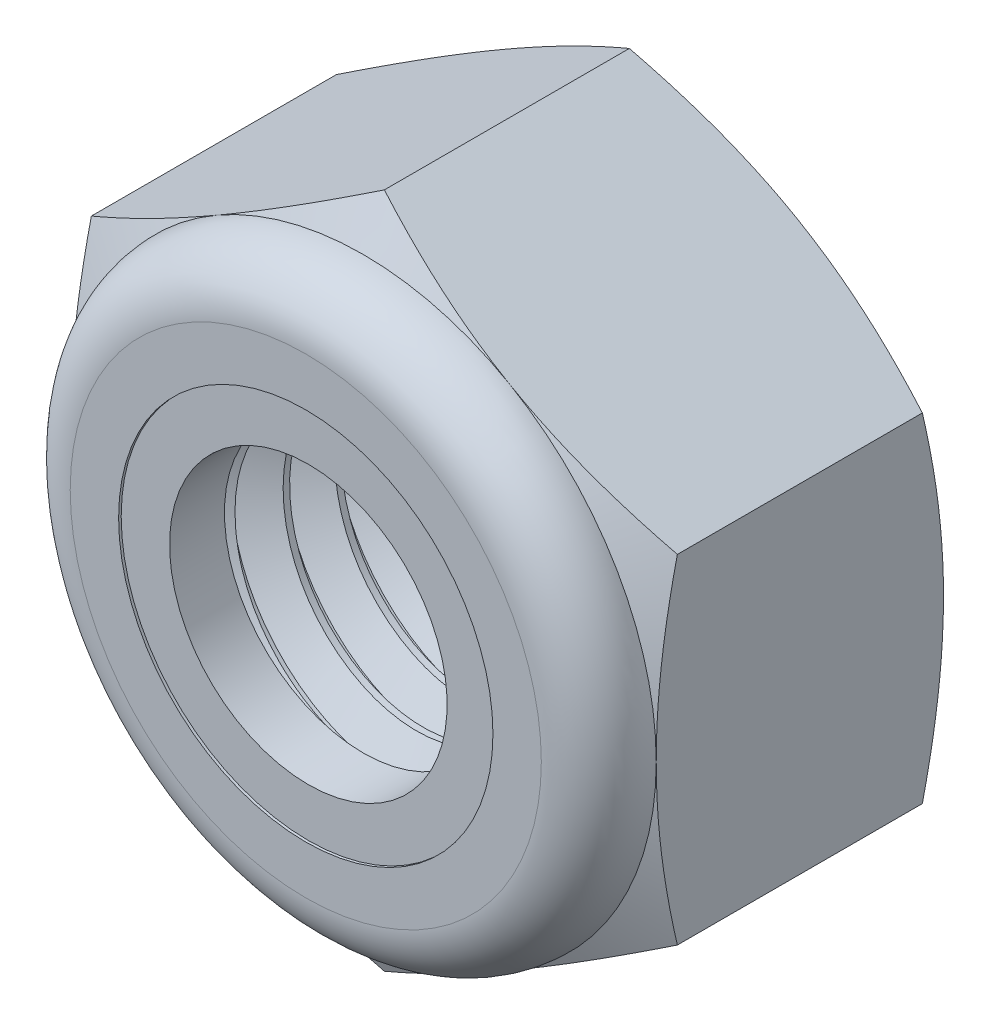
SolidWorks part; units mm, degrees
ref_plane "Front Plane" through (0, 0, 0) normal (0, 0, 1) x (1, 0, 0)
ref_plane "Top Plane" through (0, 0, 0) normal (0, 1, 0) x (1, 0, 0)
ref_plane "Right Plane" through (0, 0, 0) normal (1, 0, 0) x (0, 0, -1)
sketch "Sketch1" plane through (0, 0, 0) normal (0, 0, 1) x (1, 0, 0)
  line L1 (0, 9.815) -> (-8.5, 4.9075)
  line L2 (-8.5, 4.9075) -> (-8.5, -4.9075)
  line L3 (-8.5, -4.9075) -> (0, -9.815)
  line L4 (0, -9.815) -> (8.5, -4.9075)
  line L5 (8.5, -4.9075) -> (8.5, 4.9075)
  line L6 (8.5, 4.9075) -> (0, 9.815)
  circle A0 centre (0, 0) radius 8.5 construction
  circle A1 centre (0, 0) radius 5
  point P10 (0, -5)
  point P11 (0, 5)
  point P12 (0, 8.5)
  dimension "Thread Size" = 10
  dimension "Width" = 17
sketch "Sketch2" plane through (0, 0, 0) normal (1, 0, 0) x (0, 0, -1)
  line L0 (5, 0) -> (-5, 0) construction
  line L1 (-5, 5) -> (5, 5) construction
  line L2 (-4.925, -5.4295) -> (-6.27, -5.4295) construction
  line L3 (-6.4063, 5.1624) -> (-4.9063, 5.1624) construction
  line L4 (-4.9063, 5.1624) -> (-5.6563, 3.8633) construction
  line L5 (-5.6563, 3.8633) -> (-6.4063, 5.1624) construction
  line L6 (-6.3125, 5) -> (-5, 5) construction
  line L7 (-5.75, 4.0257) -> (-5.5625, 4.0257) construction
  line L8 (-5.6563, 4.0257) -> (-5.6563, 3.8633) construction
  line L9 (-5.6563, 5) -> (-5.6563, 5.1624) construction
  line L10 (-4.9531, 5.0812) -> (-6.3594, 5.0812)
  line L11 (-6.3594, 5.0812) -> (-5.75, 4.0257)
  line L12 (-5.75, 4.0257) -> (-5.5625, 4.0257)
  line L13 (-5.5625, 4.0257) -> (-4.9531, 5.0812)
  line L14 (5, 0) -> (6.27, 0)
  line L15 (6.27, 0) -> (6.27, 11.085)
  line L16 (0, 11.085) -> (0, 9.815) construction
  line L17 (0, 9.815) -> (0, 4.9075) construction
  line L18 (5, 8.5) -> (-3.3333, 8.5) construction
  line L19 (-5.75, -4.0257) -> (-5.5625, -4.0257) construction
  line L20 (5, 8.5) -> (5, 0)
  line L21 (4.3868, 9.815) -> (-2.7202, 9.815)
  line L22 (5, 8.5) -> (4.3868, 9.815)
  line L23 (-5, 0) -> (-5, 6.8333) construction
  line L24 (-3.3333, 8.5) -> (-2.7202, 9.815)
  line L25 (6.27, 11.085) -> (-6.27, 11.085)
  line L26 (-5, 6.8333) -> (-6.27, 6.8333)
  line L27 (-6.27, 6.8333) -> (-6.27, 11.085)
  line L28 (-4.925, 6.8333) -> (-4.925, 4.0257) construction
  line L29 (-4.925, 5.4295) -> (-6.27, 5.4295)
  line L30 (-6.27, 5.4295) -> (-6.27, 0)
  line L31 (-6.27, 0) -> (-3.3333, 0)
  line L32 (-3.3333, 0) -> (-3.3333, 8.425)
  line L33 (-4.925, 5.4295) -> (-4.925, 6.8333)
  arc A0 (-3.3333, 8.5) -> (-5, 6.8333) centre (-3.3333, 6.8333) ccw
  arc A1 (-3.3333, 8.425) -> (-4.925, 6.8333) centre (-3.3333, 6.8333) ccw
  point P4 (0, 0)
  point P18 (-5.6563, 5.0812)
  point P22 (-5.6563, 5.0812)
  point P33 (0, 9.815)
  point P48 (-6.27, -5.4295)
  point P51 (-5.75, -4.0257)
  dimension "Height" = 10
  dimension "Pitch" = 1.5
  dimension "D1" = 0.1875
  dimension "D2" = 1.27
  dimension "D3" = 25
  dimension "D4" = 1.6667
  dimension "D5" = 25
  dimension "D6" = 0.075
sketch "Sketch3" plane through (0, 0, 0) normal (0, 0, 1) x (1, 0, 0)
  line L0 (0, -9.815) -> (8.5, -4.9075) construction
  line L1 (8.5, -4.9075) -> (8.5, 4.9075) construction
  line L2 (8.5, 4.9075) -> (0, 9.815) construction
  line L3 (0, 9.815) -> (-8.5, 4.9075) construction
  line L4 (-8.5, 4.9075) -> (-8.5, -4.9075) construction
  line L5 (-8.5, -4.9075) -> (0, -9.815) construction
  line L6 (0, -9.815) -> (8.5, -4.9075)
  line L7 (8.5, -4.9075) -> (8.5, 4.9075)
  line L8 (8.5, 4.9075) -> (0, 9.815)
  line L9 (0, 9.815) -> (-8.5, 4.9075)
  line L10 (-8.5, 4.9075) -> (-8.5, -4.9075)
  line L11 (-8.5, -4.9075) -> (0, -9.815)
  circle A0 centre (0, 0) radius 5 construction
  circle A1 centre (0, 0) radius 5
extrude "Boss-Extrude1" add sketch "Sketch3" along normal mid plane 10
sketch "Sketch4" plane through (0, 0, 0) normal (1, 0, 0) x (0, 0, -1)
  line L0 (6.27, 11.085) -> (-6.27, 11.085) construction
  line L1 (-6.27, 6.8333) -> (-6.27, 11.085) construction
  line L2 (-5, 6.8333) -> (-6.27, 6.8333) construction
  line L3 (-3.3333, 8.5) -> (-2.7202, 9.815) construction
  line L4 (4.3868, 9.815) -> (-2.7202, 9.815) construction
  line L5 (5, 8.5) -> (4.3868, 9.815) construction
  line L6 (5, 8.5) -> (5, 0) construction
  line L7 (5, 0) -> (6.27, 0) construction
  line L8 (6.27, 0) -> (6.27, 11.085) construction
  line L9 (-6.27, 5.4295) -> (-6.27, 0) construction
  line L10 (-6.27, 0) -> (-3.3333, 0) construction
  line L11 (-3.3333, 0) -> (-3.3333, 8.425) construction
  line L12 (-4.925, 5.4295) -> (-4.925, 6.8333) construction
  line L13 (-4.925, 5.4295) -> (-6.27, 5.4295) construction
  line L14 (6.27, 11.085) -> (-6.27, 11.085)
  line L15 (-6.27, 6.8333) -> (-6.27, 11.085)
  line L16 (-5, 6.8333) -> (-6.27, 6.8333)
  line L17 (-3.3333, 8.5) -> (-2.7202, 9.815)
  line L18 (4.3868, 9.815) -> (-2.7202, 9.815)
  line L19 (5, 8.5) -> (4.3868, 9.815)
  line L20 (5, 8.5) -> (5, 0)
  line L21 (5, 0) -> (6.27, 0)
  line L22 (6.27, 0) -> (6.27, 11.085)
  line L23 (-6.27, 5.4295) -> (-6.27, 0)
  line L24 (-6.27, 0) -> (-3.3333, 0)
  line L25 (-3.3333, 0) -> (-3.3333, 8.425)
  line L26 (-4.925, 5.4295) -> (-4.925, 6.8333)
  line L27 (-4.925, 5.4295) -> (-6.27, 5.4295)
  arc A0 (-3.3333, 8.5) -> (-5, 6.8333) centre (-3.3333, 6.8333) ccw construction
  arc A1 (-3.3333, 8.425) -> (-4.925, 6.8333) centre (-3.3333, 6.8333) ccw construction
  arc A2 (-3.3333, 8.5) -> (-5, 6.8333) centre (-3.3333, 6.8333) ccw
  arc A3 (-3.3333, 8.425) -> (-4.925, 6.8333) centre (-3.3333, 6.8333) ccw
revolve "Cut-Revolve1" cut sketch "Sketch4" angle 360 about L0
sketch "Sketch5" plane through (0, 0, 0) normal (1, 0, 0) x (0, 0, -1)
  line L0 (-4.925, 6.8333) -> (-4.925, 4.0257) construction
  line L1 (-3.3333, 0) -> (-3.3333, 8.425) construction
  line L2 (-4.925, 6.8333) -> (-4.925, 4.0257)
  line L3 (-3.3333, 4.0257) -> (-3.3333, 8.425)
  line L4 (-4.925, 4.0257) -> (-3.3333, 4.0257)
  arc A0 (-3.3333, 8.425) -> (-4.925, 6.8333) centre (-3.3333, 6.8333) ccw construction
  arc A1 (-3.3333, 8.425) -> (-4.925, 6.8333) centre (-3.3333, 6.8333) ccw
revolve "Revolve1" add sketch "Sketch5" angle 360 about L0
sketch "Sketch6" plane through (0, 0, 5) normal (0, 0, 1) x (1, 0, 0)
  circle A0 centre (0, 0) radius 5 construction
  circle A1 centre (0, 0) radius 5
curve "Helix/Spiral1" pitch 1.5 height 11.5 radius 5 centre (0, 0, 5) axis (0, 0, -1) start towards (0, 1, 0)
sketch "Sketch7" plane through (0, 0, 0) normal (1, 0, 0) x (0, 0, -1)
  line L0 (-6.3594, 5.0812) -> (-5.75, 4.0257) construction
  line L1 (-5.75, 4.0257) -> (-5.5625, 4.0257) construction
  line L2 (-5.5625, 4.0257) -> (-4.9531, 5.0812) construction
  line L3 (-4.9531, 5.0812) -> (-6.3594, 5.0812) construction
  line L4 (-6.3594, 5.0812) -> (-5.75, 4.0257)
  line L5 (-5.75, 4.0257) -> (-5.5625, 4.0257)
  line L6 (-5.5625, 4.0257) -> (-4.9531, 5.0812)
  line L7 (-4.9531, 5.0812) -> (-6.3594, 5.0812)
sweep "Sweep1" add profiles "Sketch7" path "Helix/Spiral1"
sketch "Sketch8" plane through (0, 0, -5) normal (0, 0, -1) x (-1, 0, 0)
  circle A2 centre (0, 0) radius 5.0812
  point P2 (0, 5.0812)
extrude "Cut-Extrude1" cut sketch "Sketch8" along normal through all and the other way through all draft 60
sketch "Sketch9" plane through (0, 0, 3.3333) normal (0, 0, 1) x (1, 0, 0)
  circle A2 centre (0, 0) radius 5.0812
  circle A3 centre (0, 0) radius 4.0257 construction
  point P2 (0, 5.0812)
  point P4 (0, 4.0257)
extrude "Cut-Extrude2" cut sketch "Sketch9" along normal through all and the other way through all draft 60
equation "\"D1@Sketch2\" = \"Pitch@Sketch2\" / 8"
equation "\"D4@Sketch2\"=\"Height@Sketch2\"/6"
equation "\"D1@Boss-Extrude1\"=\"Height@Sketch2\""
equation "\"D3@Helix/Spiral1\"=\"Height@Sketch2\"+\"Pitch@Sketch2\""
equation "\"D4@Helix/Spiral1\"=\"Pitch@Sketch2\""
equation "\"D6@Sketch2\"=\"Pitch@Sketch2\"*0.05"
